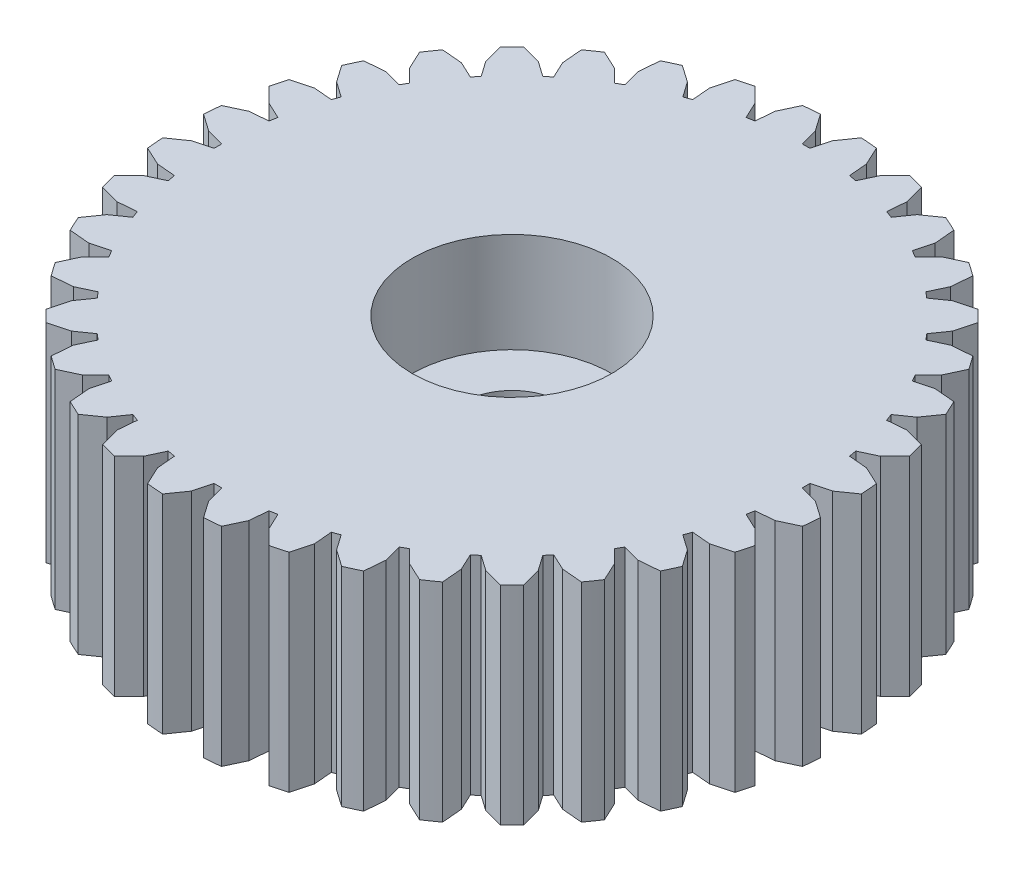
SolidWorks part; units mm, degrees
ref_plane "Front Plane" through (0, 0, 0) normal (0, 0, 1) x (1, 0, 0)
ref_plane "Top Plane" through (0, 0, 0) normal (0, 1, 0) x (1, 0, 0)
ref_plane "Right Plane" through (0, 0, 0) normal (1, 0, 0) x (0, 0, -1)
sketch "Sketch1" plane through (0, 0, 0) normal (0, 1, 0) x (1, 0, 0)
  circle A0 centre (0, 0) radius 10.0584
  dimension "D1" = 20.1168
extrude "Boss-Extrude1" add sketch "Sketch1" along normal blind 6.35
sketch "Sketch2" plane through (0, 6.35, 0) normal (0, 1, 0) x (1, 0, 0)
  circle A0 centre (0, 0) radius 1.524
  dimension "D1" = 3.048
extrude "Cut-Extrude1" cut sketch "Sketch2" against normal through all
sketch "Sketch3" plane through (0, 6.35, 0) normal (0, 1, 0) x (1, 0, 0)
  circle A0 centre (0, 0) radius 3.048
  dimension "D1" = 6.096
extrude "Cut-Extrude2" cut sketch "Sketch3" against normal blind 3.048
sketch "Sketch4" plane through (0, 0, 0) normal (0, -1, 0) x (1, 0, 0)
  line L0 (-0.2646, -9.525) -> (0.2646, -9.525) construction
  line L1 (0, 0) -> (0, -12.1008) construction
  line L2 (0.2646, -9.525) -> (0.1177, -8.9767)
  line L4 (-0.2646, -9.525) -> (-0.1177, -8.9767)
  line L5 (0.2646, -9.525) -> (0.7726, -10.2505)
  line L6 (-0.2646, -9.525) -> (-0.7901, -10.2756)
  line L7 (0.0472, -8.9767) -> (0.1177, -8.9767)
  line L8 (0.0472, -8.9767) -> (-0.1177, -8.9767)
  line L9 (-0.7901, -10.2756) -> (0.7726, -10.2505)
  dimension "D1" = 75
  dimension "D2" = 75
  dimension "D3" = 125
  dimension "D4" = 125
extrude "Cut-Extrude3" cut sketch "Sketch4" against normal through all
pattern_circular "CirPattern1" count 36 over 360 about axis through (0, 0, 0) along (0, 1, 0) of "Cut-Extrude3"
